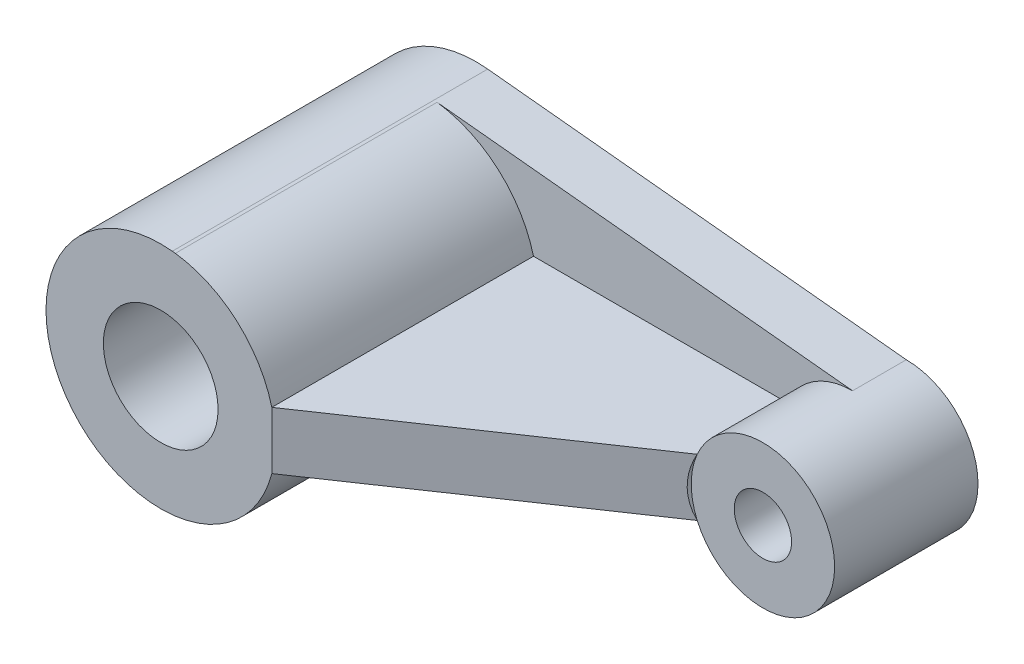
SolidWorks part; units mm, degrees
note: The reader was unsure of these and kept them because the rebuilt part matched: shared geometry of "Sketch2<3>".
ref_plane "Front Plane" through (0, 0, 0) normal (1, 0, 0) x (0, 1, 0)
ref_plane "Top Plane" through (0, 0, 0) normal (0, 0, 1) x (0, 1, 0)
ref_plane "Right Plane" through (0, 0, 0) normal (0, 1, 0) x (-1, 0, 0)
sketch "Sketch1" plane through (0, 0, 0) normal (0, 0, 1) x (0, 1, 0)
  line L0 (0, 0) -> (0, 38682.383) construction
  line L1 (0, 0) -> (38682.383, 0) construction
  line L2 (-31.8369, -3.2272) -> (-20, -120)
  line L3 (31.8369, -3.2272) -> (20, -120)
  arc A0 (31.8369, -3.2272) -> (-31.8369, -3.2272) centre (0, 0) ccw
  circle A1 centre (0, 0) radius 16
  circle A2 centre (0, -120) radius 8
  arc A3 (-20, -120) -> (20, -120) centre (0, -120) ccw
  dimension "D1" = 64
  dimension "D2" = 32
  dimension "D3" = 40
  dimension "D4" = 16
  dimension "D5" = 120
extrude "Boss-Extrude1" add sketch "Sketch1" along normal blind 15
sketch "Sketch2" plane through (0, 0, 15) normal (0, 0, 1) x (1, 0, 0)
  circle A0 centre (0, 0) radius 32.0118
  circle A1 centre (120, 0) radius 20
  circle M2 centre (0, 0) radius 16
  arc M3 (3.2272, 31.8369) -> (3.2272, -31.8369) centre (0, 0) ccw
  line M4 (3.2272, -31.8369) -> (120, -20)
  arc M5 (120, -20) -> (120, 20) centre (120, 0) ccw
  line M6 (120, 20) -> (3.2272, 31.8369)
  circle M7 centre (120, 0) radius 8
extrude "Boss-Extrude2" add sketch "Sketch2" along normal blind 73 contours A0 M4 M6 M3 M2
extrude "Boss-Extrude3" add sketch "Sketch2<3>" along normal blind 25 contours A1 M5 M7
sketch "Sketch2<3>" plane through (0, 0, 15) normal (0, 0, 1) x (1, 0, 0) same geometry as "Sketch2"
sketch "Sketch5" plane through (0, 0, 15) normal (0, 0, 1) x (1, 0, 0)
  line L0 (32.0118, -33.9014) -> (32.0118, -49.9014)
  line L1 (0, 0) -> (50000, 0) construction
  line L2 (30.996, 8) -> (101.6697, 8)
  line L3 (30.996, -8) -> (101.6697, -8)
  arc A0 (4.0909, -31.7493) -> (4.0909, 31.7493) centre (0, 0) ccw construction
  arc A2 (120, 20) -> (120, -20) centre (120, 0) ccw construction
  arc A3 (4.0909, -31.7493) -> (4.0909, 31.7493) centre (0, 0) ccw construction
  arc A4 (30.996, 8) -> (30.996, -8) centre (-0.7839, 0) ccw
  arc A5 (101.6697, -8) -> (101.6697, 8) centre (120, 0) ccw
  point P3 (32.0118, -41.9014)
  arc M5 (120, -20) -> (120, 20) centre (120, 0) cw
  arc M7 (4.0909, 31.7493) -> (4.0909, -31.7493) centre (0, 0) cw
  dimension "D1" = 16
extrude "Boss-Extrude7" add sketch "Sketch5" along normal blind 73 contours L1 L2 M7 M5 | L1 L3 M7 M5
sketch "Sketch6" plane through (0, -8, 0) normal (0, -1, 0) x (1, 0, 0)
  line L0 (30.996, 88) -> (101.6697, 40)
  line L1 (101.6697, 40) -> (101.6697, 88)
  line L2 (101.6697, 88) -> (30.996, 88)
extrude "Cut-Extrude1" cut sketch "Sketch6" against normal blind 73
